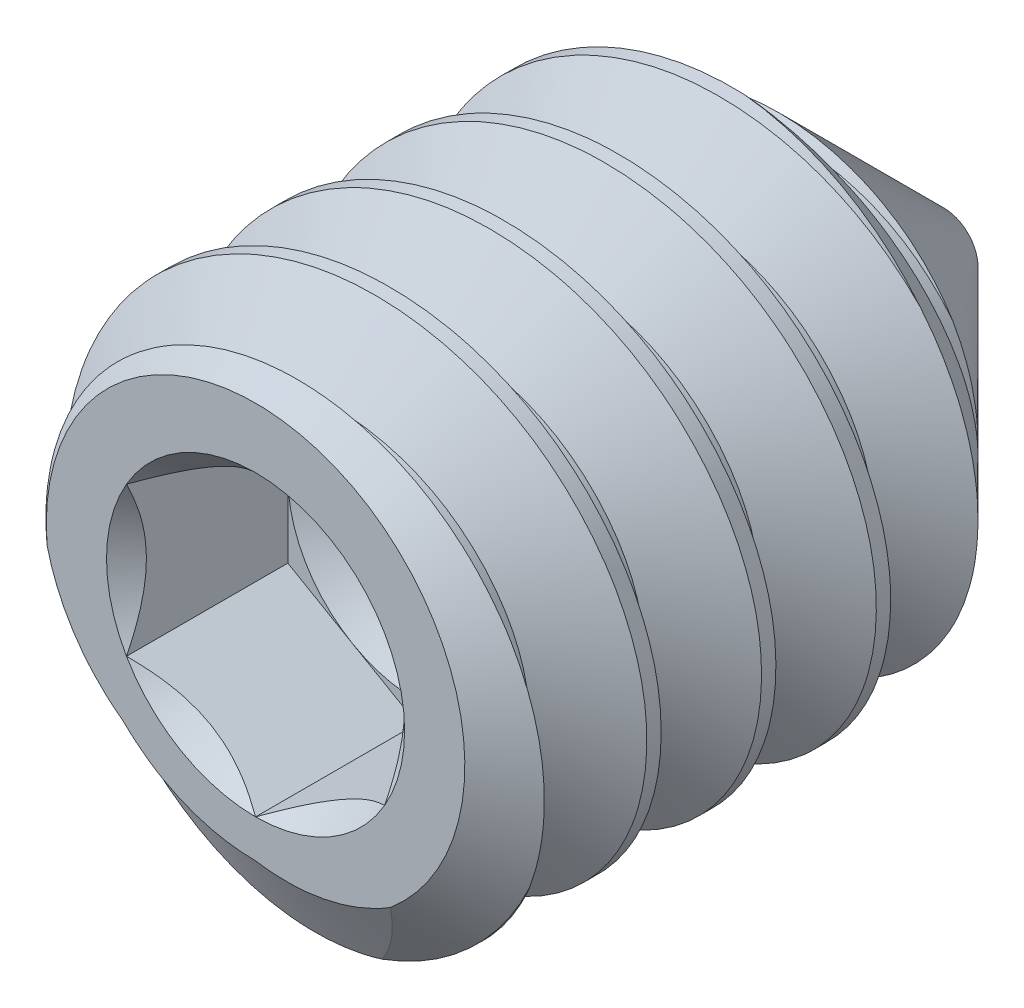
SolidWorks part; units mm, degrees
ref_plane "Front" through (0, 0, 0) normal (0, 0, 1) x (1, 0, 0)
ref_plane "Top" through (0, 0, 0) normal (0, 1, 0) x (1, 0, 0)
ref_plane "Right" through (0, 0, 0) normal (1, 0, 0) x (0, 0, -1)
sketch "Sketch22" plane through (0, 0, 0) normal (1, 0, 0) x (0, 0, -1)
  line L0 (-3.175, 0) -> (-3.175, 1.9304)
  line L1 (-3.175, 1.9304) -> (-2.8371, 2.413)
  line L2 (-2.8371, 2.413) -> (1.0757, 2.413)
  line L3 (1.0757, 2.413) -> (3.175, 0.3137)
  line L4 (-3.175, 1.9304) -> (-3.175, -1.9304) construction
  line L5 (3.175, 0) -> (-3.175, 0)
  line L6 (0, 2.413) -> (0, -2.413) construction
  line L8 (3.175, 0.3137) -> (3.175, 0)
  line L9 (-3.175, -2.413) -> (3.175, -2.413) construction
  line L10 (3.175, 0.3137) -> (3.175, -0.3137) construction
  line L11 (3.175, -0.3137) -> (1.0757, -2.413) construction
  line L13 (3.175, 0.3137) -> (2.8613, 0) construction
  line L15 (2.8613, 0) -> (3.175, -0.3137) construction
  dimension "D1" = 90
  dimension "Dia" = 4.826
  dimension "D2" = 0.6274
  dimension "Length" = 6.35
  dimension "D3" = 35
  dimension "D4" = 90
  dimension "D7" = 3.8608
revolve "Revolve1" add sketch "Sketch22" angle 360 about L5
ref_plane "Plane1" through (0, 0, -3.175) normal (0, 0, 1) x (1, 0, 0)
sketch "Sketch27" plane through (0, 0, -3.175) normal (0, 0, 1) x (1, 0, 0)
  circle A0 centre (0, 0) radius 2.413 construction
  circle A1 centre (0, 0) radius 2.413
curve "Helix/Spiral1" pitch 1.0583 height 7.4083 radius 2.413 centre (0, 0, -3.175) axis (0, 0, 1) start towards (0, 1, 0)
sketch "Sketch28" plane through (0, 0, 0) normal (1, 0, 0) x (0, 0, -1)
  line L0 (3.175, 2.413) -> (4.101, 2.413)
  line L1 (4.101, 2.413) -> (3.7042, 1.7256)
  line L2 (3.7042, 1.7256) -> (3.5719, 1.7256)
  line L3 (3.5719, 1.7256) -> (3.175, 2.413)
  line L4 (3.3734, 2.0693) -> (3.9026, 2.0693) construction
  line L6 (-2.8371, 2.413) -> (1.0757, 2.413) construction
  line L7 (3.175, 2.6543) -> (3.175, -2.6543) construction
  dimension "D1" = 0.1323
  dimension "D2" = 0.5292
  dimension "D3" = 60
sweep "Cut-Sweep2" cut profiles "Sketch28" path "Helix/Spiral1"
sketch "Sketch23" plane through (0, 0, 3.175) normal (0, 0, 1) x (1, 0, 0)
  line L1 (0, 1.3748) -> (-1.1906, 0.6874)
  line L2 (-1.1906, 0.6874) -> (-1.1906, -0.6874)
  line L3 (-1.1906, -0.6874) -> (0, -1.3748)
  line L4 (0, -1.3748) -> (1.1906, -0.6874)
  line L5 (1.1906, -0.6874) -> (1.1906, 0.6874)
  line L6 (1.1906, 0.6874) -> (0, 1.3748)
  circle A0 centre (0, 0) radius 1.1906 construction
  dimension "Hex" = 2.3813
extrude "Cut-Extrude10" cut sketch "Sketch23" against normal blind 1.4883
sketch "Sketch24" plane through (0, 0, 3.175) normal (0, 0, 1) x (1, 0, 0)
  circle A0 centre (0, 0) radius 1.3748
extrude "Cut-Extrude11" cut sketch "Sketch24" against normal through all draft 45
sketch "Sketch26" plane through (0, 0, 1.6867) normal (0, 0, 1) x (1, 0, 0)
  circle A0 centre (0, 0) radius 1.1906 construction
  circle A1 centre (0, 0) radius 1.1906
extrude "Cut-Extrude12" cut sketch "Sketch26" against normal through all draft 60
sketch "Sketch30" plane through (0, 0, 0) normal (1, 0, 0) x (0, 0, -1)
  line L0 (-2.8371, 2.413) -> (1.0757, 2.413) construction
  line L1 (-3.175, 0) -> (-3.175, 1.9304) construction
  line L3 (-3.175, -2.413) -> (3.175, -2.413) construction
  point P0 (-3.175, 2.413)
  point P1 (1.0757, 2.413)
  point P2 (1.0757, -2.413)
  point P11 (-0.5118, -2.413)
  dimension "D1" = 1.5875
equation "\"D7@Sketch22\"=\"Dia@Sketch22\"*.8"
equation "\"D1@Sketch28\" = \"D4@Helix/Spiral1\" * .125"
equation "\"D3@Helix/Spiral1\" = \"Length@Sketch22\" + \"D4@Helix/Spiral1\""
equation "\"D1@Sketch30\" = \"D4@Helix/Spiral1\" * 1.5"
equation "\"hex Depth@Cut-Extrude10\" = \"Hex@Sketch23\" * .625"
equation "\"D2@Sketch28\" = \"D4@Helix/Spiral1\" * .5"
equation "\"D2@Sketch22\" = \"Dia@Sketch22\" * .13"
equation "\"D4@Sketch22\" = \"D1@Sketch22\""
